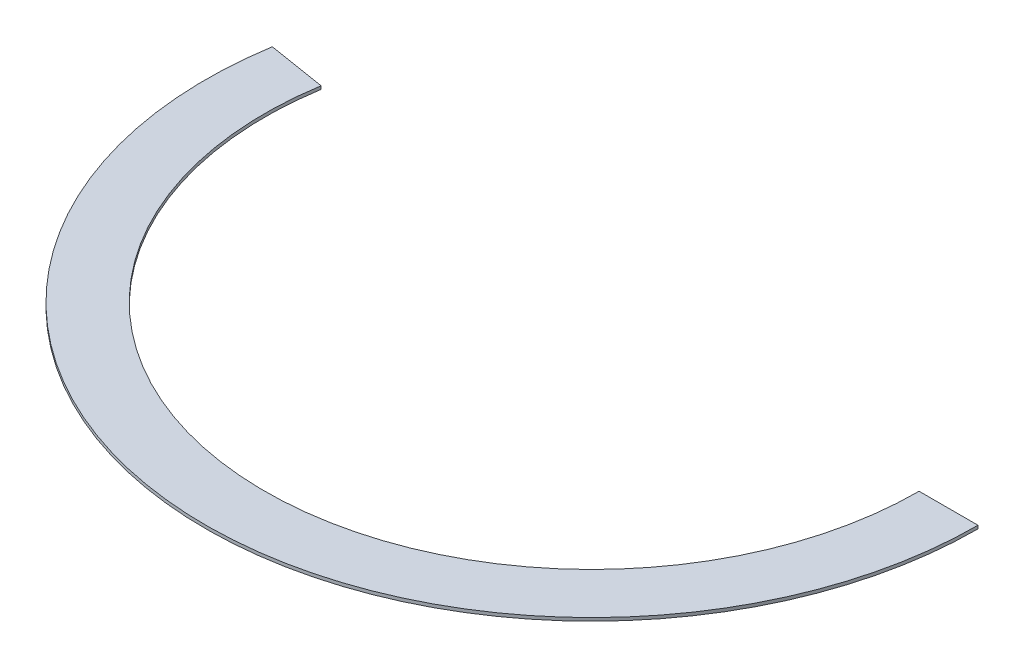
SolidWorks part; units mm, degrees
ref_plane "Front Plane" through (0, 0, 0) normal (0, 0, 1) x (1, 0, 0)
ref_plane "Top Plane" through (0, 0, 0) normal (0, 1, 0) x (1, 0, 0)
ref_plane "Right Plane" through (0, 0, 0) normal (1, 0, 0) x (0, 0, -1)
sketch "Sketch3" plane through (0, 0, 0) normal (0, 1, 0) x (1, 0, 0)
  line L0 (-71.297, 11.5093) -> (-84.1309, 13.581)
  line L1 (72.22, 0) -> (85.22, 0)
  arc A0 (-84.1309, 13.581) -> (85.22, 0) centre (0, 0) ccw
  arc A1 (72.22, 0) -> (-71.297, 11.5093) centre (0, 0) cw
  dimension "D1" = 13
  dimension "D2" = 85.22
  dimension "D3" = 170.83
extrude "Boss-Extrude1" add sketch "Sketch3" along normal blind 0.7
